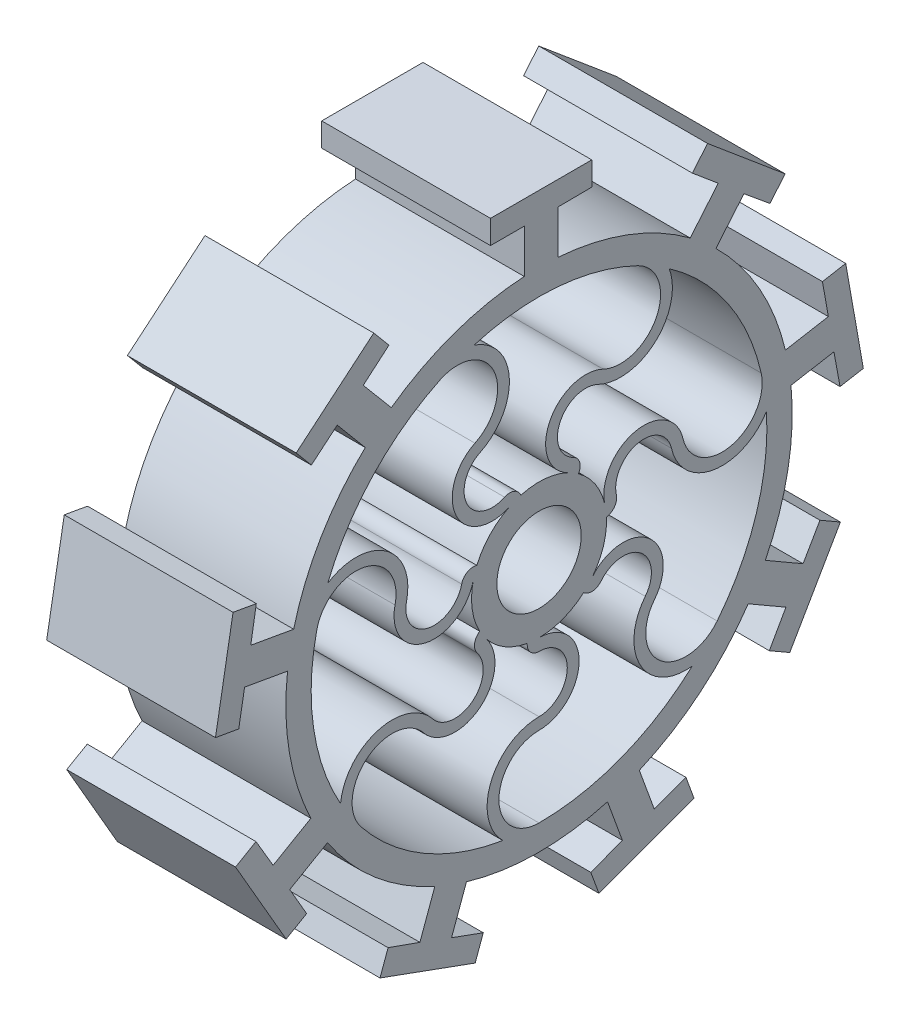
SolidWorks part; units mm, degrees
ref_plane "Front Plane" through (0, 0, 0) normal (0, 0, 1) x (1, 0, 0)
ref_plane "Top Plane" through (0, 0, 0) normal (0, 1, 0) x (1, 0, 0)
ref_plane "Right Plane" through (0, 0, 0) normal (1, 0, 0) x (0, 0, -1)
sketch "Sketch1" plane through (0, 0, 0) normal (1, 0, 0) x (0, 0, -1)
  circle A0 centre (0, 0) radius 25.4 construction
  circle A1 centre (0, 0) radius 3.175
  circle A2 centre (0, 0) radius 5.08
  circle A3 centre (0, 0) radius 19.05
  circle A4 centre (0, 0) radius 17.145
  dimension "D1" = 50.8
  dimension "D2" = 38.1
  dimension "D3" = 34.29
  dimension "D4" = 6.35
  dimension "D5" = 10.16
extrude "Boss-Extrude1" add sketch "Sketch1" along normal blind 12.7 contours A3 A4 | A2 A1 region at (0, 0, 4.9363) region at (0, 0, 18.5112)
sketch "Sketch2" plane through (0, 0, 0) normal (1, 0, 0) x (0, 0, -1)
  circle A0 centre (0, 0) radius 5.08
  circle A1 centre (0, 0) radius 17.145
  arc A2 (0, -11.1125) -> (0, -5.08) centre (0, -8.0963) ccw
  arc A3 (0, -11.1125) -> (0, -17.145) centre (0, -14.1288) ccw
  arc A6 (0, -10.2235) -> (-2.7239, -16.9272) centre (0, -14.1288) ccw
  arc A7 (0, -10.2235) -> (0, -5.969) centre (0, -8.0963) ccw
  arc A8 (0, -5.969) -> (-0.8856, -5.0022) centre (0, -5.08) cw
  point P15 (0, 0)
  dimension "D1" = 10.16
  dimension "D2" = 34.29
  dimension "D3" = 0.889
  dimension "D4" = 0
extrude "Boss-Extrude2" add sketch "Sketch2" along normal up to surface (12.7 mm away) contours A8 A7 A6 A1 A3 A2 A0 region at (0, -10.6813, 0.5074) up to face at (12.7, 0, -3.175)
pattern_circular "CirPattern1" count 7 over 360 about axis through (12.7, 0, 0) along (1, 0, 0) of "Boss-Extrude2"
sketch "Sketch3" plane through (0, 0, 0) normal (1, 0, 0) x (0, 0, -1)
  line L1 (3.9697, 24.0763) -> (-3.6502, 24.0763)
  line L2 (-3.6502, 24.0763) -> (-3.6502, 22.2983)
  line L3 (-3.6502, 22.2983) -> (-1.1102, 22.2983)
  line L4 (-1.1102, 22.2983) -> (-1.1102, 19.0176)
  line L6 (3.9697, 24.0763) -> (3.9697, 22.2983)
  line L7 (1.4298, 22.2769) -> (1.4298, 18.9963)
  line L8 (3.9697, 22.2983) -> (1.4298, 22.2769)
  circle A0 centre (0, 0) radius 19.05 construction
  circle A1 centre (0, 0) radius 19.05
  point P1 (0, 0)
  point P4 (3.9695, 22.2769)
  point P5 (3.9697, 24.0763)
  point P16 (0, 0)
  dimension "D5" = 2.5401
  dimension "D1" = 2.54
  dimension "D2" = 1.778
  dimension "D3" = 2.54
  dimension "D4" = 5.08
extrude "Boss-Extrude3" add sketch "Sketch3" along a picked direction on the side of the normal blind 12.7 contours A1 L7 L8 L6 L1 L2 L3 L4 region at (0, 22.2306, -0.1629)
pattern_circular "CirPattern2" count 9 over 360 about axis through (12.7, 0, 0) along (1, 0, 0) of "Boss-Extrude3"
